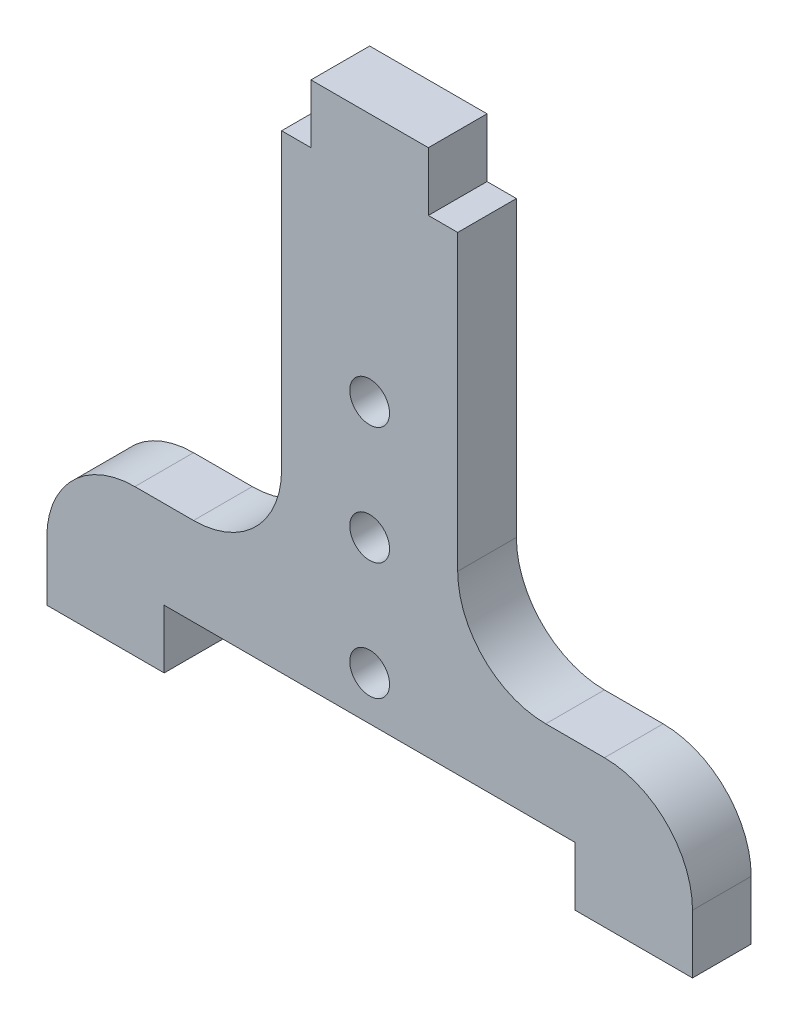
SolidWorks part; units mm, degrees
material "Custom Plastic"
ref_plane "Front Plane" through (0, 0, 0) normal (0, 0, 1) x (1, 0, 0)
ref_plane "Top Plane" through (0, 0, 0) normal (0, 1, 0) x (1, 0, 0)
ref_plane "Right Plane" through (0, 0, 0) normal (1, 0, 0) x (0, 0, -1)
sketch "Sketch1" plane through (0, 0, 0) normal (0, 0, 1) x (1, 0, 0)
  line L1 (-34.925, -25.4) -> (34.925, -25.4)
  line L2 (-34.925, -25.4) -> (-34.925, 25.4)
  line L3 (-34.925, 25.4) -> (34.925, 25.4)
  line L4 (34.925, -25.4) -> (34.925, 25.4)
  line L5 (-34.925, -25.4) -> (34.925, 25.4) construction
  line L6 (-34.925, 25.4) -> (34.925, -25.4) construction
  point P0 (0, 0)
  dimension "D1" = 69.85
  dimension "D2" = 50.8
extrude "Base" add sketch "Sketch1" along normal blind 6.35
sketch "Sketch6" plane through (0, 0, 6.35) normal (0, 0, 1) x (1, 0, 0)
  line L0 (34.925, 25.4) -> (-34.925, 25.4) construction
  line L1 (-6.35, 25.4) -> (6.35, 25.4)
  line L2 (-6.35, 25.4) -> (-6.35, 31.75)
  line L3 (-6.35, 31.75) -> (6.35, 31.75)
  line L4 (6.35, 25.4) -> (6.35, 31.75)
  line L5 (0, -25.4) -> (0, 25.4) construction
  line L6 (-34.925, -25.4) -> (34.925, -25.4) construction
  line L7 (22.225, -25.4) -> (22.225, -31.75)
  line L8 (-34.925, -25.4) -> (-22.225, -25.4)
  line L9 (-34.925, -25.4) -> (-34.925, -31.75)
  line L10 (-34.925, -31.75) -> (-22.225, -31.75)
  line L11 (-22.225, -25.4) -> (-22.225, -31.75)
  line L12 (34.925, -31.75) -> (22.225, -31.75)
  line L13 (34.925, -25.4) -> (34.925, -31.75)
  line L14 (34.925, -25.4) -> (22.225, -25.4)
  point P7 (0, 25.4)
  dimension "D1" = 12.7
  dimension "D2" = 6.35
  dimension "D3" = 6.35
  dimension "D4" = 12.7
extrude "Boss-Extrude1" add sketch "Sketch6" against normal blind 6.35
sketch "Sketch7" plane through (0, 0, 6.35) normal (0, 0, 1) x (1, 0, 0)
  line L1 (-6.35, 25.4) -> (-34.925, 25.4) construction
  line L2 (-9.525, 25.4) -> (-9.525, -15.875)
  line L4 (-9.525, -15.875) -> (-34.925, -15.875)
  line L5 (-34.925, 25.4) -> (-34.925, -31.75) construction
  line L6 (-22.225, -25.4) -> (22.225, -25.4) construction
  line L7 (0, -25.4) -> (0, 31.75) construction
  line L8 (6.35, 31.75) -> (-6.35, 31.75) construction
  line L9 (-9.525, 25.4) -> (-34.925, 25.4)
  line L10 (-34.925, 25.4) -> (-34.925, -15.875)
  line L11 (34.925, 25.4) -> (34.925, -15.875)
  line L12 (9.525, 25.4) -> (34.925, 25.4)
  line L13 (9.525, -15.875) -> (34.925, -15.875)
  line L15 (9.525, 25.4) -> (9.525, -15.875)
  dimension "D1" = 9.525
  dimension "D2" = 9.525
extrude "Cut-Extrude1" cut sketch "Sketch7" against normal through all
sketch "Motor mounting sketch" plane through (0, 0, 6.35) normal (0, 0, 1) x (1, 0, 0)
  line L0 (-34.925, -20.6375) -> (34.925, -20.6375) construction
  line L1 (34.925, -31.75) -> (34.925, -15.875) construction
  line L2 (-34.925, -15.875) -> (-34.925, -31.75) construction
  line L3 (0, 25.4) -> (0, -20.6375) construction
  line L4 (-22.225, -25.4) -> (22.225, -25.4) construction
  line L7 (-22.225, -25.4) -> (22.225, -25.4) construction
  line L9 (9.525, 25.4) -> (6.35, 25.4) construction
  point P12 (0, -20.6375)
  point P15 (0, 17.4625)
  point P20 (0, -7.9375)
  point P21 (0, 4.7625)
  dimension "D1" = 4.7625
  dimension "D2" = 12.7
  dimension "D3" = 90
  dimension "D4" = 12.7
  dimension "D5" = 12.7
sketch "Sketch8" plane through (0, 0, 6.35) normal (0, 0, 1) x (1, 0, 0)
  line L0 (9.525, 25.4) -> (9.525, -15.875) construction
  line L1 (6.35, -25.4) -> (9.525, -25.4)
  line L2 (6.35, -25.4) -> (6.35, 11.1125)
  line L3 (6.35, 11.1125) -> (9.525, 11.1125)
  line L4 (9.525, -25.4) -> (9.525, 11.1125)
  line L5 (-22.225, -25.4) -> (22.225, -25.4) construction
  dimension "D1" = 6.35
  dimension "D3" = 6.35
extrude "Boss-Extrude3" add sketch "Sketch8" against normal blind 6.35
hole_wizard "#8 Clearance Hole1" positions "Sketch5" profile "Sketch4" hole size "#8" standard "ANSI Inch" end condition through all
sketch "Sketch5" plane through (0, 0, 0) normal (0, 0, -1) x (-1, 0, 0)
  point P3 (0, -20.6375)
  point P31 (0, -7.9375)
  point P34 (0, 4.7625)
sketch "Sketch4" plane through (0, -20.6375, 0) normal (1, 0, 0) x (0, 1, 0)
  line L0 (0, 0) -> (0, 6.35)
  line L1 (0, 6.35) -> (2.1526, 6.35)
  line L2 (2.1526, 6.35) -> (2.1526, 0)
  line L5 (2.1526, 0) -> (0, 0)
  line L11 (0, -6.35) -> (0, 107.95) construction
  dimension "Thru Hole Dia." = 4.3053
  dimension "Thru Hole Depth" = 6.35
fillet "Fillet1" radius 9.525 4 edges at (34.925, -15.875, 3.175) (9.525, -15.875, 3.175) (-9.525, -15.875, 3.175) (-34.925, -15.875, 3.175)
equation "\"MAT_THICKNESS\"=0.25"
equation "\"D1@Base\"=\"MAT_THICKNESS\""
equation "\"D2@Sketch6\" = \"MAT_THICKNESS\""
equation "\"D3@Sketch6\"=\"MAT_THICKNESS\""
equation "\"D1@Boss-Extrude1\"=\"MAT_THICKNESS\""
equation "\"D1@Boss-Extrude3\"=\"MAT_THICKNESS\""
